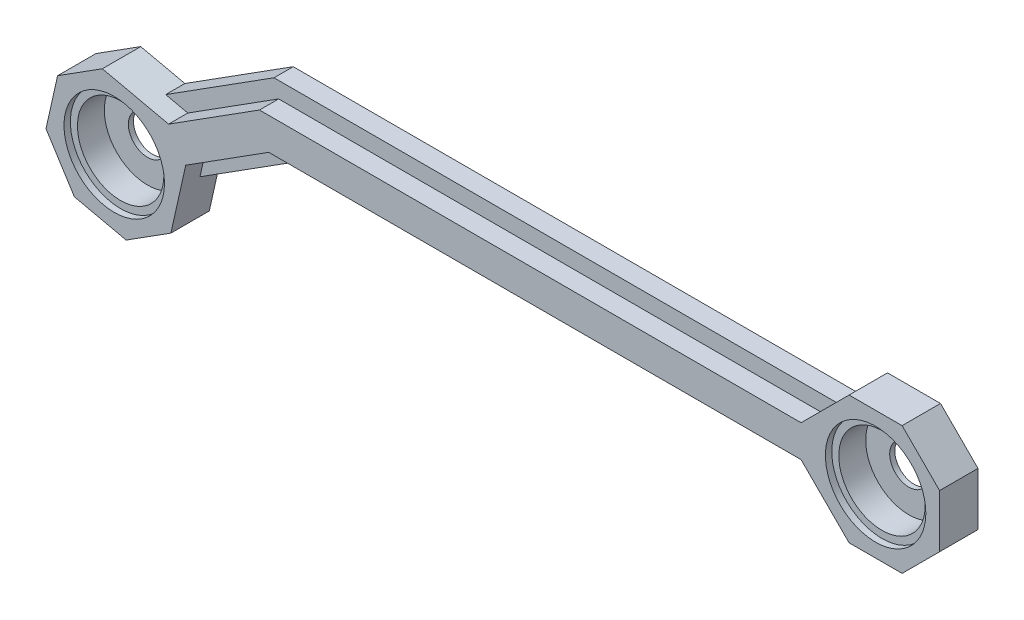
SolidWorks part; units mm, degrees
material "AISI 1020"
ref_plane "Front Plane" through (0, 0, 0) normal (0, 0, 1) x (1, 0, 0)
ref_plane "Top Plane" through (0, 0, 0) normal (0, 1, 0) x (1, 0, 0)
ref_plane "Right Plane" through (0, 0, 0) normal (1, 0, 0) x (0, 0, -1)
sketch "Sketch1" plane through (0, 0, 0) normal (0, 0, 1) x (1, 0, 0)
  line L0 (0, 0) -> (-95.55, 0) construction
  line L1 (-95.55, 0) -> (-118.9664, -14.8548) construction
  line L2 (-108.5682, -14.1796) -> (-94.0978, -5)
  line L3 (4.1421, 10) -> (-4.1421, 10)
  line L4 (-4.1421, 10) -> (-10, 4.1421)
  line L6 (-10, -4.1421) -> (-4.1421, -10)
  line L7 (-4.1421, -10) -> (4.1421, -10)
  line L8 (4.1421, -10) -> (10, -4.1421)
  line L9 (10, -4.1421) -> (10, 4.1421)
  line L10 (10, 4.1421) -> (4.1421, 10)
  line L11 (-127.8209, -8.6294) -> (-129.6295, -16.7139)
  line L12 (-129.6295, -16.7139) -> (-125.1918, -23.7093)
  line L13 (-125.1918, -23.7093) -> (-117.1073, -25.5178)
  line L14 (-117.1073, -25.5178) -> (-110.1119, -21.0801)
  line L15 (-110.1119, -21.0801) -> (-108.3033, -12.9957)
  line L17 (-112.7411, -6.0003) -> (-120.8255, -4.1917)
  line L18 (-120.8255, -4.1917) -> (-127.8209, -8.6294)
  line L19 (-94.0978, -5) -> (-9.1421, -5)
  line L20 (-97.0022, 5) -> (-9.1421, 5)
  line L21 (-113.925, -5.7354) -> (-97.0022, 5)
  line L22 (-94.0978, -5) -> (-97.0022, 5)
  line L23 (-120.8255, -4.1917) -> (-110.4747, -6.5073)
  line L24 (-4.1421, 10) -> (-11.6421, 2.5)
  line L25 (-4.1421, -10) -> (-11.6421, -2.5)
  line L26 (-110.1119, -21.0801) -> (-107.7963, -10.7294)
  line L27 (-11.6421, 2.5) -> (-96.2761, 2.5)
  line L28 (-96.2761, 2.5) -> (-110.4747, -6.5073)
  line L29 (-94.8239, -2.5) -> (-107.7963, -10.7294)
  line L30 (-11.6421, -2.5) -> (-94.8239, -2.5)
  line L31 (-94.8239, -2.5) -> (-107.7963, -10.7294)
  line L32 (-108.3033, -12.9957) -> (-110.5222, -9.498) [skipped]
  line L33 (-10, 0) -> (-10, -4.1421) [skipped]
  arc A0 (-7.0711, -7.0711) -> (-7.0711, 7.0711) centre (0, 0) ccw construction
  arc A1 (-116.7833, -5.096) -> (-109.2076, -17.0379) centre (-118.9664, -14.8548) ccw construction
  circle A2 centre (-118.9664, -14.8548) radius 3
  circle A3 centre (-0.8766, 0) radius 3
  dimension "D1" = 95.55
  dimension "D2" = 20
  dimension "D3" = 20
  dimension "D4" = 147.61
  dimension "D5" = 10
  dimension "D6" = 26.75
  dimension "D7" = 10
  dimension "D8" = 5
extrude "Boss-Extrude1" add sketch "Sketch1" against normal blind 6 contours L29 L22 L28 L23 L17 L18 L11 L12 L13 L14 L15 L26 A2 | L30 L25 L6 L7 L8 L9 L10 L3 L4 L24 L27 L22 A3 region at (-115.3283, -12.5378, 0) region at (-30.7802, 0.0041, 0)
sketch "Sketch2" plane through (0, 0, 0) normal (0, 0, 1) x (1, 0, 0)
  line L0 (-113.925, -5.7354) -> (-110.4747, -6.5073)
  line L1 (-110.4747, -6.5073) -> (-96.2761, 2.5)
  line L2 (-96.2761, 2.5) -> (-11.6421, 2.5)
  line L3 (-11.6421, 2.5) -> (-9.1421, 5)
  line L4 (-9.1421, 5) -> (-97.0022, 5)
  line L5 (-97.0022, 5) -> (-113.925, -5.7354)
  line L6 (-108.5682, -14.1796) -> (-107.7963, -10.7294)
  line L7 (-107.7963, -10.7294) -> (-94.8239, -2.5)
  line L8 (-94.8239, -2.5) -> (-11.6421, -2.5)
  line L9 (-11.6421, -2.5) -> (-9.1421, -5)
  line L10 (-9.1421, -5) -> (-94.0978, -5)
  line L11 (-94.0978, -5) -> (-108.5682, -14.1796)
extrude "Boss-Extrude2" add sketch "Sketch2" against normal blind 3
sketch "Sketch3" plane through (0, 0, -6) normal (0, 0, -1) x (-1, 0, 0)
  circle A0 centre (0, 0) radius 7.85
  circle A1 centre (118.9664, -14.8548) radius 7.85
extrude "Cut-Extrude1" cut sketch "Sketch3" against normal blind 1
sketch "Sketch4" plane through (0, 0, -6) normal (0, 0, -1) x (-1, 0, 0)
  circle A0 centre (0, 0) radius 6.75
  circle A1 centre (118.9664, -14.8548) radius 6.75
extrude "Cut-Extrude2" cut sketch "Sketch4" against normal blind 5.2
sketch "Sketch5" plane through (0, 0, 0) normal (0, 0, 1) x (1, 0, 0)
  line L1 (-6.0261, -3.3388) -> (4.2729, -3.3388)
  line L2 (-6.0261, -3.3388) -> (-6.0261, 3.3388)
  line L3 (-6.0261, 3.3388) -> (4.2729, 3.3388)
  line L4 (4.2729, -3.3388) -> (4.2729, 3.3388)
  line L5 (-6.0261, -3.3388) -> (4.2729, 3.3388) construction
  line L6 (-6.0261, 3.3388) -> (4.2729, -3.3388) construction
  point P0 (-0.8766, 0)
extrude "Boss-Extrude3" add sketch "Sketch5" against normal blind 0.8
sketch "Sketch6" plane through (0, 0, 0) normal (0, 0, 1) x (1, 0, 0)
  circle A0 centre (0, 0) radius 3
extrude "Cut-Extrude3" cut sketch "Sketch6" against normal blind 0.8
sketch "Sketch7" plane through (0, 0, -6) normal (0, 0, -1) x (-1, 0, 0)
  circle A0 centre (0, 0) radius 3
  circle A1 centre (0, 0) radius 9.0718
  circle A2 centre (118.9664, -14.8548) radius 3
  circle A3 centre (118.9664, -14.8548) radius 8.5301
extrude "Boss-Extrude5" add sketch "Sketch7" against normal blind 6 contours A1 | A0 | A3 | A2
sketch "Sketch8" plane through (0, 0, 0) normal (0, 0, 1) x (1, 0, 0)
  circle A0 centre (-118.9664, -14.8548) radius 7.85
  circle A1 centre (0, 0) radius 7.85
extrude "Cut-Extrude4" cut sketch "Sketch8" against normal blind 1
sketch "Sketch9" plane through (0, 0, 0) normal (0, 0, 1) x (1, 0, 0)
  circle A0 centre (-118.9664, -14.8548) radius 6.75
  circle A1 centre (0, 0) radius 6.75
extrude "Cut-Extrude5" cut sketch "Sketch9" against normal blind 5.2
sketch "Sketch10" plane through (0, 0, -3) normal (0, 0, -1) x (-1, 0, 0)
  line L0 (9.1421, -5) -> (11.6421, -2.5)
  line L1 (11.6421, -2.5) -> (94.8239, -2.5)
  line L2 (94.8239, -2.5) -> (107.7963, -10.7294)
  line L3 (107.7963, -10.7294) -> (108.5682, -14.1796)
  line L4 (108.5682, -14.1796) -> (94.0978, -5)
  line L5 (94.0978, -5) -> (9.1421, -5) construction
  line L6 (108.5682, -14.1796) -> (94.0978, -5) construction
  line L7 (94.0978, -5) -> (9.1421, -5)
  line L8 (9.1421, 5) -> (11.6421, 2.5)
  line L9 (11.6421, 2.5) -> (96.2761, 2.5)
  line L10 (96.2761, 2.5) -> (110.4747, -6.5073)
  line L11 (110.4747, -6.5073) -> (113.925, -5.7354)
  line L12 (113.925, -5.7354) -> (97.0022, 5)
  line L13 (97.0022, 5) -> (9.1421, 5)
extrude "Boss-Extrude6" add sketch "Sketch10" along normal blind 3
sketch "Sketch11" plane through (0, 0, 0) normal (0, 0, 1) x (1, 0, 0)
  line L0 (-107.7963, -10.7294) -> (-108.5682, -14.1796)
  line L1 (-108.5682, -14.1796) -> (-94.0978, -5)
  line L2 (-94.0978, -5) -> (-9.1421, -5)
  line L3 (-9.1421, -5) -> (-11.6421, -2.5)
  line L4 (-11.6421, -2.5) -> (-94.8239, -2.5)
  line L5 (-94.8239, -2.5) -> (-107.7963, -10.7294)
  line L6 (-107.7963, -10.7294) -> (-108.5682, -14.1796)
  line L7 (-107.7963, -10.7294) -> (-94.8239, -2.5)
  line L8 (-94.8239, -2.5) -> (-11.6421, -2.5)
  line L9 (-11.6421, -2.5) -> (-9.1421, -5)
  line L10 (-9.1421, -5) -> (-94.0978, -5)
  line L11 (-108.5682, -14.1796) -> (-94.0978, -5)
  line L12 (-113.925, -5.7354) -> (-110.4747, -6.5073)
  line L13 (-110.4747, -6.5073) -> (-96.2761, 2.5)
  line L14 (-96.2761, 2.5) -> (-11.6421, 2.5)
  line L15 (-11.6421, 2.5) -> (-9.1421, 5)
  line L16 (-9.1421, 5) -> (-97.0022, 5)
  line L17 (-97.0022, 5) -> (-113.925, -5.7354)
extrude "Cut-Extrude10" cut sketch "Sketch11" against normal blind 3 contours L16 L17 L12 L13 L14 L15 | L4 L5 L0 L1 L2 L3 region at (-60.3441, -4.463, 0) region at (-62.4802, 2.8917, 0)
equation "\"A\"= 100"
equation "\"B\"= 100"
equation "\"C\"= 100"
equation "\"D\"= 100"
equation "\"E\"= 100"
